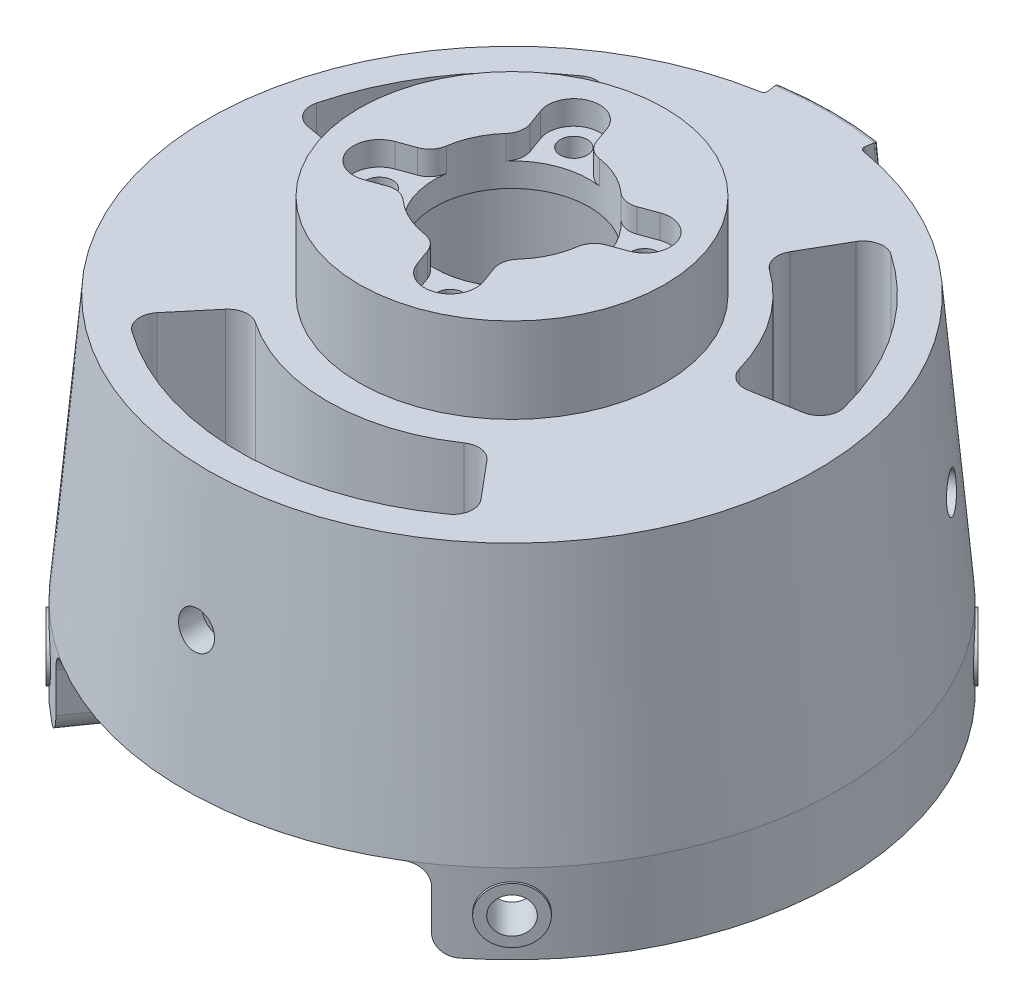
SolidWorks part; units mm, degrees
ref_plane "Front Plane" through (0, 0, 0) normal (0, 0, 1) x (1, 0, 0)
ref_plane "Top Plane" through (0, 0, 0) normal (0, 1, 0) x (1, 0, 0)
ref_plane "Right Plane" through (0, 0, 0) normal (1, 0, 0) x (0, 0, -1)
sketch "Sketch1" plane through (0, 0, 0) normal (0, 1, 0) x (1, 0, 0)
  line L0 (-29.85, 23.9174) -> (-29.85, -23.9174)
  line L1 (29.85, 23.9174) -> (29.85, -23.9174)
  line L2 (-29.85, 0) -> (29.85, 0) construction
  arc A0 (-29.85, -23.9174) -> (29.85, -23.9174) centre (0, 0) ccw
  arc A1 (29.85, 23.9174) -> (-29.85, 23.9174) centre (0, 0) ccw
  point P9 (0, 0)
  dimension "D1" = 59.7
  dimension "D2" = 76.5
extrude "Boss-Extrude1" add sketch "Sketch1" along normal blind 44
sketch "Sketch2" plane through (0, 44, 0) normal (0, 1, 0) x (1, 0, 0)
  line L0 (-4.4463, 12.216) -> (0, 0) construction
  line L1 (0, 13) -> (0, 0) construction
  circle A0 centre (0, 0) radius 13
  point P3 (-4.4463, 12.216)
  dimension "D1" = 26
  dimension "D2" = 20
hole_wizard "CBORE for M3 SHCS1" positions "Sketch2" profile "Sketch3" counterbore size "M3" standard "ANSI Metric" end condition through all
sketch "Sketch3" plane through (-4.4463, 44, -12.216) normal (1, 0, 0) x (0, 0, 1)
  line L0 (0, 0) -> (0, 44)
  line L1 (0, 44) -> (1.7, 44)
  line L3 (1.7, 44) -> (1.7, 3)
  line L4 (1.7, 3) -> (3.25, 3)
  line L5 (3.25, 3) -> (3.25, 0)
  line L7 (3.25, 0) -> (0, 0)
  line L11 (0, -6.35) -> (0, 107.95) construction
  dimension "Thru Hole Dia." = 3.4
  dimension "Thru Hole Depth" = 44
  dimension "C'Bore Dia." = 6.5
  dimension "C'Bore Depth" = 3
ref_axis "Axis1" through (0, 44, 0) along (0, -1, 0)
pattern_circular "CirPattern1" count 4 over 360 about axis through (0, 44, 0) along (0, -1, 0) of "CBORE for M3 SHCS1"
sketch "Sketch4" plane through (0, 0, 0) normal (0, -1, 0) x (1, 0, 0)
  circle A0 centre (0, 0) radius 16.2
  dimension "D1" = 32.4
extrude "Cut-Extrude1" cut sketch "Sketch4" against normal blind 38
sketch "Sketch5" plane through (0, 44, 0) normal (0, 1, 0) x (1, 0, 0)
  circle A0 centre (0, 0) radius 9.7
extrude "Cut-Extrude2" cut sketch "Sketch5" against normal through all
ref_plane "Plane1" through (0, 0, -38.25) normal (0, 0, -1) x (-1, 0, 0)
sketch "Sketch7" plane through (0, 0, 0) normal (0, -1, 0) x (1, 0, 0)
  line L5 (29.85, 23.9174) -> (29.85, -23.9174)
  line L6 (-29.85, 23.9174) -> (-29.85, -23.9174)
  arc A0 (-29.85, -23.9174) -> (29.85, -23.9174) centre (0, 0) ccw construction
  arc A1 (29.85, 23.9174) -> (-29.85, 23.9174) centre (0, 0) ccw construction
  arc A2 (-29.85, -23.9174) -> (29.85, -23.9174) centre (0, 0) ccw
  arc A3 (29.85, 23.9174) -> (-29.85, 23.9174) centre (0, 0) ccw
  circle A4 centre (0, 0) radius 41.1622
  dimension "D1" = 82.3245
extrude "Boss-Extrude2" add sketch "Sketch7" against normal up to surface (44 mm away) up to face at (0, 44, 9.7)
sketch "Sketch9" plane through (0, 0, 0) normal (1, 0, 0) x (0, 0, -1)
  line L0 (-41.1622, 0) -> (-37.3127, 44)
  line L1 (-37.3127, 44) -> (-41.1622, 44)
  line L2 (-41.1622, 44) -> (-41.1622, 0) construction
  line L3 (-41.1622, 44) -> (-41.1622, 0)
  line L4 (0, 0) -> (0, 44) construction
  line L5 (41.1622, 44) -> (-41.1622, 44) construction
  dimension "D1" = 5
revolve "Cut-Revolve2" cut sketch "Sketch9" angle 360 about L4
sketch "Sketch10" plane through (0, 0, 0) normal (1, 0, 0) x (0, 0, -1)
  line L0 (-19.2, 44) -> (-19.2, 33.2871)
  line L1 (37.3127, 44) -> (-37.3127, 44) construction
  line L2 (-19.2, 33.2871) -> (-38.25, 33.2871)
  line L3 (-37.3127, 44) -> (-41.1622, 0) construction
  line L4 (-38.25, 33.2871) -> (-37.3127, 44)
  line L5 (-37.3127, 44) -> (-19.2, 44)
  line L6 (0, 0) -> (0, 44) construction
  line L10 (-41.1622, 0) -> (41.1622, 0) construction
  line L11 (-16.2, 0) -> (16.2, 0) construction
  line L12 (-16.2, 0) -> (16.2, 0) construction
  line L13 (37.3127, 44) -> (-37.3127, 44) construction
  dimension "D1" = 10.7129
  dimension "D2" = 33.2871
  dimension "D3" = 3
revolve "Cut-Revolve3" cut sketch "Sketch10" angle 360 about L6
sketch "Sketch13" plane through (0, 33.2871, 0) normal (0, 1, 0) x (1, 0, 0)
  line L0 (0, -34.25) -> (0, -38.25) construction
  circle A0 centre (0, 0) radius 34.25
  circle A1 centre (0, 0) radius 19.2 construction
  circle A2 centre (0, 0) radius 19.2
  circle A3 centre (0, 0) radius 38.25 construction
  dimension "D1" = 4
extrude "Cut-Extrude3" cut sketch "Sketch13" against normal through all both and the other way through all
sketch "Sketch16" plane through (0, 0, 0) normal (0, -1, 0) x (1, 0, 0)
  line L0 (0, -34.25) -> (0, -19.2) construction
  line L1 (-17.125, -29.6614) -> (-9.6, -16.6277)
  line L2 (17.125, -29.6614) -> (9.6, -16.6277)
  line L3 (-33.7297, -5.9475) -> (-18.9083, -3.334)
  line L4 (-22.0155, 26.237) -> (-12.3415, 14.7081)
  line L5 (22.0155, 26.237) -> (12.3415, 14.7081)
  line L6 (33.7297, -5.9475) -> (18.9083, -3.334)
  line L7 (0, 0) -> (-32.1845, 11.7142) construction
  circle A1 centre (0, 0) radius 34.25 construction
  circle A2 centre (0, 0) radius 19.2 construction
  arc A3 (-9.6, -16.6277) -> (9.6, -16.6277) centre (0, 0) ccw
  arc A4 (-17.125, -29.6614) -> (17.125, -29.6614) centre (0, 0) ccw
  arc A5 (-22.0155, 26.237) -> (-33.7297, -5.9475) centre (0, 0) ccw
  arc A6 (-12.3415, 14.7081) -> (-18.9083, -3.334) centre (0, 0) ccw
  arc A7 (22.0155, 26.237) -> (33.7297, -5.9475) centre (0, 0) cw
  arc A8 (12.3415, 14.7081) -> (18.9083, -3.334) centre (0, 0) cw
  point P19 (0, 0)
  dimension "D1" = 15.05
  dimension "D3" = 60
  dimension "D4" = 110
  dimension "D2" = 2
extrude "Boss-Extrude4" add sketch "Sketch16" against normal up to surface (33.2871 mm away) up to face at (0, 33.2871, 34.25)
sketch "Sketch17" plane through (0, 33.2871, 0) normal (0, 1, 0) x (1, 0, 0)
  line L0 (0, -19.2) -> (0, -23.2) construction
  circle A0 centre (0, 0) radius 23.2
  circle A1 centre (0, 0) radius 19.2 construction
  circle A2 centre (0, 0) radius 19.2
  dimension "D1" = 4
extrude "Boss-Extrude5" add sketch "Sketch17" against normal up to surface (33.2871 mm away) up to face at (-20.8663, 0, -14.6107)
fillet "Fillet2" radius 2.5 12 edges at (-14.9127, 16.6435, 17.7722) (-22.0155, 16.6435, 26.237) (22.0155, 16.6435, 26.237) (14.9127, 16.6435, 17.7722) (-17.125, 16.6435, -29.6614) (-33.7297, 16.6435, -5.9475) (-22.8475, 16.6435, -4.0286) (-11.6, 16.6435, -20.0918) (33.7297, 16.6435, -5.9475) (17.125, 16.6435, -29.6614) (11.6, 16.6435, -20.0918) (22.8475, 16.6435, -4.0286)
ref_plane "Plane2" through (0, 16.6435, 0) normal (0, -1, 0) x (-1, 0, 0)
sketch "Sketch18" plane through (0, 16.6435, 0) normal (0, -1, 0) x (-1, 0, 0)
  line L0 (0, 0) -> (28.056, 19.645) construction
  line L1 (0, 0) -> (-28.056, 19.645) construction
  line L2 (0, 0) -> (0, -34.25) construction
  line L3 (0, 0) -> (-10.437, -32.621) construction
  line L4 (0, 0) -> (10.437, -32.621) construction
  arc A0 (33.1566, 8.5849) -> (19.4074, 28.2209) centre (0, 0) ccw construction
  arc A1 (-19.4074, 28.2209) -> (-33.1566, 8.5849) centre (0, 0) ccw construction
  arc A2 (-19.8812, -27.8891) -> (19.8812, -27.8891) centre (0, 0) ccw construction
  arc A3 (-19.8812, -27.8891) -> (0, -34.25) centre (0, 0) ccw construction
  arc A4 (0, -34.25) -> (19.8812, -27.8891) centre (0, 0) ccw construction
ref_plane "Plane4" through (-28.056, 16.6435, -19.645) normal (-0.8192, 0, -0.5736) x (-0.5736, 0, 0.8192)
sketch "Sketch20" plane through (-28.056, 16.6435, -19.645) normal (-0.8192, 0, -0.5736) x (-0.5736, 0, 0.8192)
  circle A0 centre (0, 0) radius 2.25
  dimension "D1" = 4.5
extrude "Cut-Extrude5" cut sketch "Sketch20" against normal blind 10 and the other way through all
sketch "Sketch21" plane through (-28.056, 16.6435, -19.645) normal (-0.8192, 0, -0.5736) x (-0.5736, 0, 0.8192)
  line L1 (4.0415, 0) -> (2.0207, 3.5)
  line L2 (2.0207, 3.5) -> (-2.0207, 3.5)
  line L3 (-2.0207, 3.5) -> (-4.0415, 0)
  line L4 (-4.0415, 0) -> (-2.0207, -3.5)
  line L5 (-2.0207, -3.5) -> (2.0207, -3.5)
  line L6 (2.0207, -3.5) -> (4.0415, 0)
  circle A0 centre (0, 0) radius 3.5 construction
  dimension "D1" = 4.0415
  dimension "D2" = 7
extrude "Cut-Extrude6" cut sketch "Sketch21" against normal blind 10 and the other way blind 2.5
pattern_circular "CirPattern2" count 3 over 250 about axis through (0, 0, 0) along (0, 1, 0) of "Cut-Extrude5", "Cut-Extrude6"
sketch "Sketch22" plane through (0, 44, 0) normal (0, 1, 0) x (1, 0, 0)
  line L2 (-12.216, -4.4463) -> (12.216, 4.4463) construction
  line L3 (-13.3276, -1.3923) -> (11.1044, 7.5003) construction
  line L4 (-11.1044, -7.5003) -> (13.3276, 1.3923) construction
  line L5 (-4.4463, 12.216) -> (4.4463, -12.216) construction
  line L6 (-1.3923, 13.3276) -> (7.5003, -11.1044) construction
  line L7 (-7.5003, 11.1044) -> (1.3923, -13.3276) construction
  line L8 (-11.1044, -7.5003) -> (-1.9424, -4.1656)
  line L9 (-1.9424, -4.1656) -> (1.3923, -13.3276)
  line L10 (7.5003, -11.1044) -> (4.1656, -1.9424)
  line L11 (4.1656, -1.9424) -> (13.3276, 1.3923)
  line L12 (11.1044, 7.5003) -> (1.9424, 4.1656)
  line L13 (1.9424, 4.1656) -> (-1.3923, 13.3276)
  line L14 (-7.5003, 11.1044) -> (-4.1656, 1.9424)
  line L15 (-4.1656, 1.9424) -> (-13.3276, -1.3923)
  arc A0 (-13.3276, -1.3923) -> (-11.1044, -7.5003) centre (-12.216, -4.4463) ccw
  arc A1 (1.3923, -13.3276) -> (7.5003, -11.1044) centre (4.4463, -12.216) ccw
  arc A2 (13.3276, 1.3923) -> (11.1044, 7.5003) centre (12.216, 4.4463) ccw
  arc A3 (-1.3923, 13.3276) -> (-7.5003, 11.1044) centre (-4.4463, 12.216) ccw
  arc A10 (-13.3276, -1.3923) -> (-11.1044, -7.5003) centre (-12.216, -4.4463) ccw construction
  arc A11 (13.3276, 1.3923) -> (11.1044, 7.5003) centre (12.216, 4.4463) ccw construction
  circle A12 centre (12.216, 4.4463) radius 3.25 construction
  arc A13 (-1.3923, 13.3276) -> (-7.5003, 11.1044) centre (-4.4463, 12.216) ccw construction
  arc A14 (1.3923, -13.3276) -> (7.5003, -11.1044) centre (4.4463, -12.216) ccw construction
  circle A15 centre (4.4463, -12.216) radius 3.25 construction
  point P2 (0, 0)
  point P11 (0, 0)
extrude "temporary_probnably" cut sketch "Sketch22" against normal up to surface (3 mm away) up to face at (-4.4463, 41, -10.516)
fillet "also_probably_temporary" radius 2.5 8 edges at (-9.6997, 42.5, 0.0718) (-7.4766, 42.5, 6.1798) (0.0718, 42.5, 9.6997) (6.1798, 42.5, 7.4766) (9.6997, 42.5, -0.0718) (7.4766, 42.5, -6.1798) (-0.0718, 42.5, -9.6997) (-6.1798, 42.5, -7.4766)
sketch "Sketch24" plane through (0, 0, 0) normal (1, 0, 0) x (0, 0, -1)
  line L0 (38.25, 33.2871) -> (-38.25, 33.2871) construction
  line L1 (-41.1622, 0) -> (41.1622, 0) construction
  line L2 (38.25, 33.2871) -> (-38.25, 33.2871) construction
  line L3 (-41.1622, 0) -> (41.1622, 0) construction
  line L4 (41.1622, 0) -> (43.1622, 0)
  line L5 (38.25, 33.2871) -> (40.25, 33.2871)
  line L6 (38.25, 33.2871) -> (41.1622, 0)
  line L7 (40.25, 33.2871) -> (43.1622, 0)
  line L8 (0, 33.2871) -> (0, 0) construction
  dimension "D1" = 2
revolve "key_1" add sketch "Sketch24" angle 9 about L8 other way angle 9
fillet "key_2" radius 0.5 6 edges at (0, 0, -43.1622) (0, 33.2871, -40.25) (-6.5243, 16.6435, -41.1926) (6.5243, 16.6435, -41.1926) (-6.2114, 16.6435, -39.2173) (6.2114, 16.6435, -39.2173)
sketch "Sketch25" plane through (0, 0, 0) normal (0, -1, 0) x (1, 0, 0)
  line L0 (-23.6097, -33.7181) -> (23.6097, 33.7181) construction
  line L1 (23.6097, -33.7181) -> (-23.6097, 33.7181) construction
  line L2 (-20.7418, 29.6224) -> (-23.6097, 33.7181)
  line L3 (-20.7418, -29.6224) -> (-23.6097, -33.7181)
  line L4 (0, 0) -> (0, 41.1622) construction
  line L6 (20.7418, 29.6224) -> (23.6097, 33.7181)
  line L7 (20.7418, -29.6224) -> (23.6097, -33.7181)
  arc A1 (-23.6097, 33.7181) -> (-23.6097, -33.7181) centre (0, 0) ccw
  circle A3 centre (0, 0) radius 36.1622 construction
  arc A4 (6.9267, -40.5753) -> (-6.9267, -40.5753) centre (0, 0) ccw construction
  arc A7 (-20.7418, -29.6224) -> (-20.7418, 29.6224) centre (0, 0) cw
  arc A20 (6.9267, -40.5753) -> (-6.9267, -40.5753) centre (0, 0) ccw construction
  arc A21 (20.7418, -29.6224) -> (20.7418, 29.6224) centre (0, 0) ccw
  arc A22 (23.6097, 33.7181) -> (23.6097, -33.7181) centre (0, 0) cw
  point P14 (0, 36.1622)
  point P16 (0, 36.1622)
  dimension "D1" = 70
  dimension "D2" = 5
extrude "Boss-Extrude6" add sketch "Sketch25" along normal blind 10
ref_plane "Plane5" through (0, -5, 0) normal (0, -1, 0) x (-1, 0, 0)
sketch "Sketch26" plane through (0, -5, 0) normal (0, -1, 0) x (-1, 0, 0)
  line L0 (0, 0) -> (41.1622, 0) construction
  line L1 (0, 0) -> (29.1061, -29.1061) construction
  arc A0 (23.6097, -33.7181) -> (23.6097, 33.7181) centre (0, 0) ccw construction
  dimension "D1" = 45
ref_plane "Plane6" through (-29.1061, -5, 29.1061) normal (-0.7071, 0, 0.7071) x (0.7071, 0, 0.7071)
sketch "Sketch28" plane through (-29.1061, -5, 29.1061) normal (-0.7071, 0, 0.7071) x (0.7071, 0, 0.7071)
  circle A0 centre (0, 0) radius 2.25
  dimension "D1" = 4.5
extrude "Cut-Extrude7" cut sketch "Sketch28" along normal through all and the other way up to surface other way up to face at (28.452, -5, 0)
sketch "Sketch29" plane through (-29.1061, -5, 29.1061) normal (-0.7071, 0, 0.7071) x (0.7071, 0, 0.7071)
  circle A0 centre (0, 0) radius 2.25 construction
  circle A1 centre (0, 0) radius 2.25
  circle A2 centre (0, 0) radius 3.5
  dimension "D1" = 7
extrude "Boss-Extrude7" add sketch "Sketch29" against normal blind 1 and the other way blind 0.25
mirror "Mirror1" about plane through (0, 0, 0) normal (0, 0, 1) of "Boss-Extrude7", "Cut-Extrude7"
mirror "Mirror2" about plane through (0, 0, 0) normal (1, 0, 0) of "Mirror1", "Boss-Extrude7"
fillet "Fillet3" radius 2.5 8 edges at (22.1757, -10, -31.6703) (22.1757, 0, -31.6703) (-22.1757, 0, -31.6703) (-22.1757, -10, -31.6703) (22.1757, -10, 31.6703) (22.1757, 0, 31.6703) (-22.1757, 0, 31.6703) (-22.1757, -10, 31.6703)
